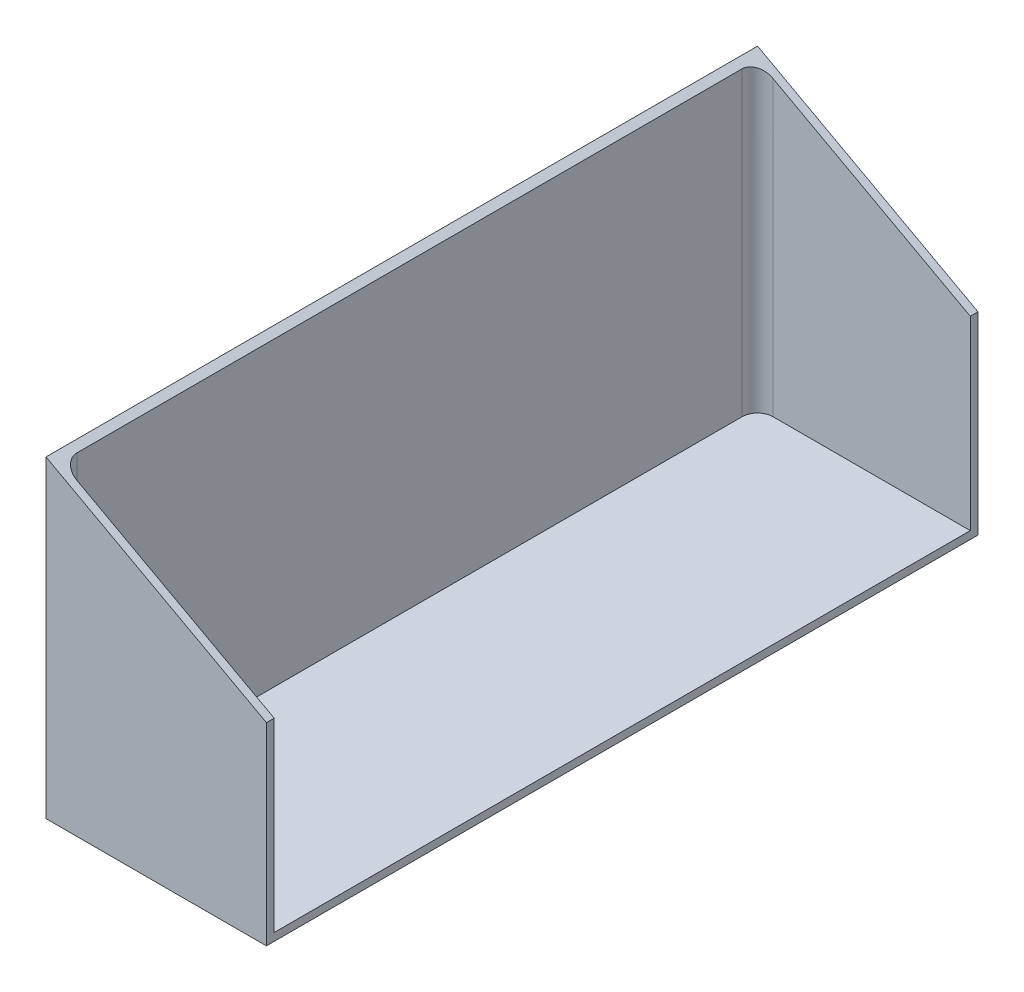
SolidWorks part; units mm, degrees
ref_plane "Front Plane" through (0, 0, 0) normal (0, 0, 1) x (1, 0, 0)
ref_plane "Top Plane" through (0, 0, 0) normal (0, 1, 0) x (1, 0, 0)
ref_plane "Right Plane" through (0, 0, 0) normal (1, 0, 0) x (0, 0, -1)
sketch "Sketch1" plane through (0, 0, 0) normal (0, 0, 1) x (1, 0, 0)
  line L0 (0, 405) -> (285, 250)
  line L5 (0, 0) -> (285, 0)
  line L6 (0, 0) -> (0, 405)
  line L8 (285, 0) -> (285, 250)
  dimension "D2" = 405
  dimension "D3" = 250
extrude "Boss-Extrude1" add sketch "Sketch1" against normal blind 10
sketch "Sketch2" plane through (0, 0, 0) normal (0, 0, 1) x (1, 0, 0)
  line L0 (0, 405) -> (0, 0) construction
  line L1 (285, 0) -> (0, 0)
  line L2 (285, 0) -> (285, 10)
  line L3 (285, 10) -> (10, 10)
  line L4 (0, 0) -> (0, 10)
  line L5 (0, 405) -> (10, 399.5614)
  line L6 (0, 0) -> (10, 0)
  line L7 (0, 0) -> (0, 405)
  line L9 (10, 10) -> (10, 399.5614)
  line L10 (285, 250) -> (0, 405) construction
  line M10 (0, 405) -> (0, 0)
  line M11 (0, 0) -> (285, 0)
  line M12 (285, 0) -> (285, 250)
  line M13 (285, 250) -> (0, 405)
  dimension "D1" = 10
  dimension "D2" = 10
extrude "Boss-Extrude2" add sketch "Sketch2" against normal blind 910 contours L3 L9 L1 M13 M10 M11 M12 region at (147.5, 4.9523, 0)
ref_plane "Symetric 1" through (0, 0, -460) normal (0, 0, -1) x (-1, 0, 0)
mirror "Mirror1" about plane through (0, 0, -460) normal (0, 0, -1) of "Boss-Extrude1"
fillet "Fillet1" radius 20 2 edges at (10, 204.7807, -10) (10, 204.7807, -910)
